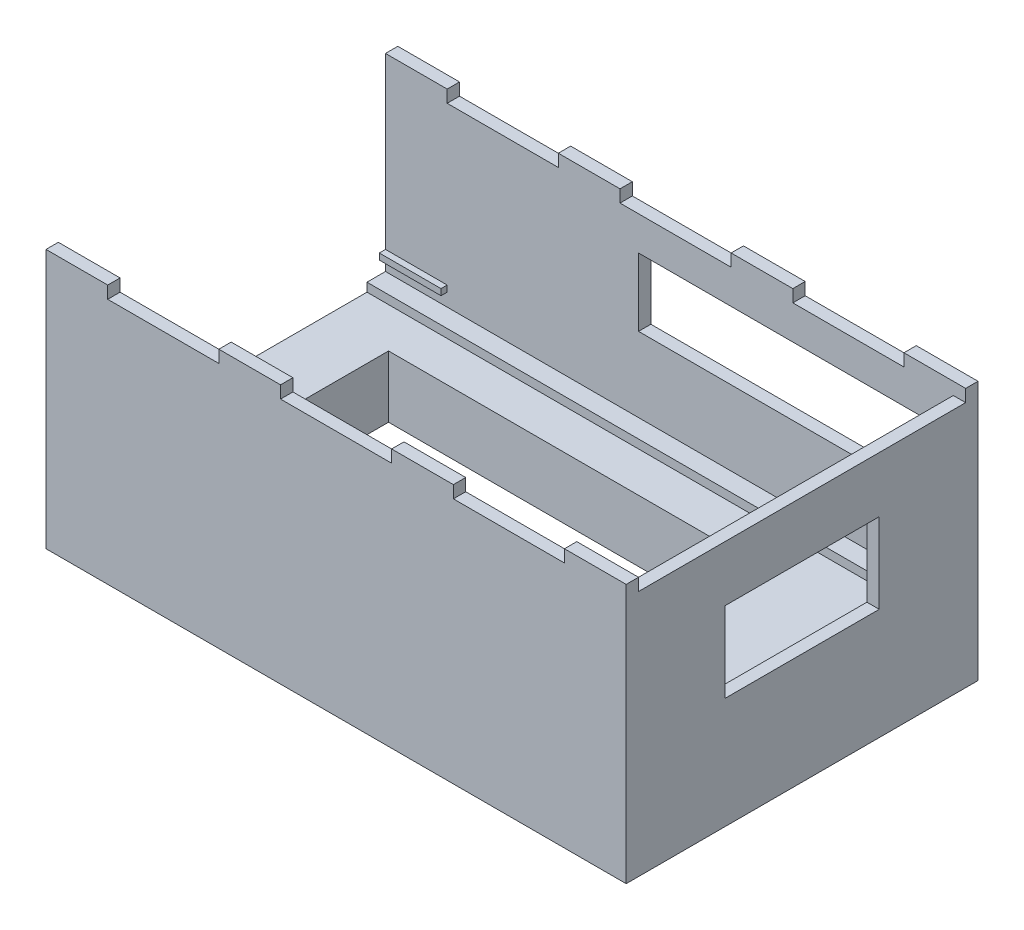
SolidWorks part; units mm, degrees
ref_plane "Front Plane" through (0, 0, 0) normal (0, 0, 1) x (1, 0, 0)
ref_plane "Top Plane" through (0, 0, 0) normal (0, 1, 0) x (1, 0, 0)
ref_plane "Right Plane" through (0, 0, 0) normal (1, 0, 0) x (0, 0, -1)
sketch "Sketch1" plane through (0, 0, 0) normal (0, 1, 0) x (1, 0, 0)
  line L1 (-30.298, 32.6459) -> (63.702, 32.6459)
  line L2 (-30.298, 32.6459) -> (-30.298, -24.3541)
  line L3 (-30.298, -24.3541) -> (63.702, -24.3541)
  line L4 (63.702, 32.6459) -> (63.702, -24.3541)
  dimension "D1" = 94
  dimension "D2" = 57
extrude "Boss-Extrude1" add sketch "Sketch1" along normal blind 10
sketch "Sketch2" plane through (0, 10, 0) normal (0, 1, 0) x (1, 0, 0)
  line L0 (-30.298, 32.6459) -> (63.702, 32.6459)
  line L1 (63.702, 32.6459) -> (63.702, -24.3541)
  line L2 (63.702, -24.3541) -> (-30.298, -24.3541)
  line L3 (-30.298, -24.3541) -> (-30.298, -22.3541)
  line L4 (-30.298, 32.6459) -> (-30.298, -24.3541) construction
  line L5 (-30.298, -22.3541) -> (61.702, -22.3541)
  line L6 (61.702, -22.3541) -> (61.702, 30.6459)
  line L7 (61.702, 30.6459) -> (-30.298, 30.6459)
  line L8 (-30.298, 30.6459) -> (-30.298, 32.6459)
  dimension "D1" = 2
  dimension "D2" = 2
  dimension "D3" = 2
extrude "Boss-Extrude2" add sketch "Sketch2" along normal blind 30
sketch "Sketch3" plane through (-30.298, 0, 0) normal (-1, 0, 0) x (0, 0, 1)
  line L0 (-30.6459, 40) -> (-30.6459, 10) construction
  line L1 (-30.6459, 10) -> (-27.6459, 10)
  line L2 (-30.6459, 10) -> (-30.6459, 11.4)
  line L3 (-30.6459, 11.4) -> (-27.6459, 11.4)
  line L4 (-27.6459, 10) -> (-27.6459, 11.4)
  line L5 (22.3541, 10) -> (19.3541, 10)
  line L6 (22.3541, 10) -> (22.3541, 11.4)
  line L7 (22.3541, 11.4) -> (19.3541, 11.4)
  line L8 (19.3541, 10) -> (19.3541, 11.4)
  line L9 (-30.6459, 14.5) -> (-29.6459, 14.5)
  line L10 (-30.6459, 14.5) -> (-30.6459, 13.5)
  line L11 (-30.6459, 13.5) -> (-29.6459, 13.5)
  line L12 (-29.6459, 14.5) -> (-29.6459, 13.5)
  line L13 (22.3541, 40) -> (22.3541, 10) construction
  line L14 (22.3541, 13.5) -> (21.3541, 13.5)
  line L15 (22.3541, 13.5) -> (22.3541, 14.5)
  line L16 (22.3541, 14.5) -> (21.3541, 14.5)
  line L17 (21.3541, 13.5) -> (21.3541, 14.5)
  point P22 (0, 0)
  dimension "D1" = 3
  dimension "D2" = 1.4
  dimension "D3" = 3
  dimension "D4" = 1.4
  dimension "D5" = 2.1
  dimension "D6" = 2.1
  dimension "D8" = 1
  dimension "D9" = 1
  dimension "D10" = 1
  dimension "D11" = 1
extrude "Boss-Extrude3" add sketch "Sketch3" against normal up to surface (92 mm away) contours L1 L4 L3 L2 | L5 L8 L7 L6 | L17 L16 L15 L14 up to face at (61.702, 25, -4.1459)
extrude "Boss-Extrude4" add sketch "Sketch3<3>" against normal blind 10 contours L12 L11 L10 L9
sketch "Sketch3<3>" plane through (-30.298, 0, 0) normal (-1, 0, 0) x (0, 0, 1) same geometry as "Sketch3"
sketch "Sketch4" plane through (0, 0, -32.6459) normal (0, 0, -1) x (-1, 0, 0)
  line L0 (-63.702, 40) -> (-63.702, 0) construction
  line L1 (-56.702, 34.5) -> (-10.702, 34.5)
  line L2 (-56.702, 34.5) -> (-56.702, 23.5)
  line L3 (-56.702, 23.5) -> (-10.702, 23.5)
  line L4 (-10.702, 34.5) -> (-10.702, 23.5)
  point P4 (-56.702, 29)
  dimension "D1" = 7
  dimension "D2" = 46
  dimension "D3" = 11
  dimension "D4" = 9
extrude "Cut-Extrude1" cut sketch "Sketch4" against normal blind 10
sketch "Sketch5" plane through (63.702, 0, 0) normal (1, 0, 0) x (0, 0, -1)
  line L0 (-24.3541, 40) -> (-24.3541, 0) construction
  line L1 (-8.3541, 31) -> (16.6459, 31)
  line L2 (-8.3541, 31) -> (-8.3541, 18)
  line L3 (-8.3541, 18) -> (16.6459, 18)
  line L4 (16.6459, 31) -> (16.6459, 18)
  line L5 (-24.3541, 40) -> (32.6459, 40) construction
  line L7 (32.6459, 40) -> (32.6459, 0) construction
  dimension "D1" = 16
  dimension "D2" = 16
  dimension "D3" = 9
  dimension "D4" = 13
extrude "Cut-Extrude2" cut sketch "Sketch5" against normal up to surface (2 mm away) up to face at (61.702, 16.8, 4.5207)
ref_plane "Plane5" through (0, 33, 0) normal (0, 1, 0) x (1, 0, 0)
sketch "Sketch7" plane through (0, 33, 0) normal (0, 1, 0) x (1, 0, 0)
  line L0 (61.702, -22.3541) -> (-30.298, -22.3541) construction
  line L1 (10.702, -22.3541) -> (61.702, -22.3541)
  line L2 (10.702, -22.3541) -> (10.702, -20.3541)
  line L3 (10.702, -20.3541) -> (59.702, -20.3541)
  line L4 (61.702, -22.3541) -> (61.702, -20.3541)
  line L5 (61.702, 27.6459) -> (61.702, -19.3541) construction
  line L6 (61.702, 30.6459) -> (61.702, -22.3541) construction
  line L8 (59.702, -20.3541) -> (59.702, 15.6459)
  line L9 (59.702, 15.6459) -> (61.702, 15.6459)
  line L10 (61.702, -20.3541) -> (61.702, 15.6459)
  dimension "D1" = 51
  dimension "D2" = 2
  dimension "D3" = 38
  dimension "D4" = 2
extrude "Boss-Extrude5" add sketch "Sketch7" against normal blind 2 contours L3 L8 L9 L10 L4 L1 L2
fillet "Fillet1" radius 1.5 2 edges at (59.702, 31, 2.3541) (35.202, 31, 20.3541) conic radius 3
ref_plane "Plane6" through (0, 34.8, 0) normal (0, 1, 0) x (1, 0, 0)
sketch "Sketch8" plane through (0, 34.8, 0) normal (0, 1, 0) x (1, 0, 0)
  line L1 (10.702, -20.3541) -> (59.702, -20.3541)
  line L2 (10.702, -20.3541) -> (10.702, -22.3541)
  line L3 (10.702, -22.3541) -> (61.702, -22.3541)
  line L4 (61.702, -20.3541) -> (61.702, -22.3541)
  line L5 (61.702, -22.3541) -> (59.702, -22.3541)
  line L6 (61.702, -22.3541) -> (61.702, 15.6459)
  line L7 (61.702, 15.6459) -> (59.702, 15.6459)
  line L8 (59.702, -20.3541) -> (59.702, 15.6459)
extrude "Boss-Extrude6" add sketch "Sketch8" along normal blind 1 contours L6 L7 L8 L1 L2 L3
sketch "Sketch9" plane through (0, 40, 0) normal (0, 1, 0) x (1, 0, 0)
  line L0 (-30.298, 30.6459) -> (61.702, 30.6459) construction
  line L1 (-30.298, 32.6459) -> (-20.298, 32.6459)
  line L2 (-30.298, 32.6459) -> (-30.298, 30.6459)
  line L3 (-30.298, 30.6459) -> (-20.298, 30.6459)
  line L4 (-20.298, 32.6459) -> (-20.298, 30.6459)
  line L5 (61.702, 30.6459) -> (-30.298, 30.6459) construction
  line L6 (-2.298, 30.6459) -> (7.702, 30.6459)
  line L7 (-2.298, 30.6459) -> (-2.298, 32.6459)
  line L8 (-2.298, 32.6459) -> (7.702, 32.6459)
  line L9 (7.702, 30.6459) -> (7.702, 32.6459)
  line L10 (63.702, 32.6459) -> (-30.298, 32.6459) construction
  line L11 (61.702, -22.3541) -> (-30.298, -22.3541) construction
  line L12 (25.702, 30.6459) -> (35.702, 30.6459)
  line L13 (25.702, 30.6459) -> (25.702, 32.6459)
  line L14 (25.702, 32.6459) -> (35.702, 32.6459)
  line L15 (35.702, 30.6459) -> (35.702, 32.6459)
  line L16 (53.702, 30.6459) -> (63.702, 30.6459)
  line L17 (53.702, 30.6459) -> (53.702, 32.6459)
  line L18 (53.702, 32.6459) -> (63.702, 32.6459)
  line L19 (63.702, 30.6459) -> (63.702, 32.6459)
  line L20 (-30.298, -24.3541) -> (-20.298, -24.3541)
  line L21 (-30.298, -24.3541) -> (-30.298, -22.3541)
  line L22 (-30.298, -22.3541) -> (-20.298, -22.3541)
  line L23 (-20.298, -24.3541) -> (-20.298, -22.3541)
  line L24 (-30.298, -24.3541) -> (63.702, -24.3541) construction
  line L25 (-2.298, -24.3541) -> (7.702, -24.3541)
  line L26 (-2.298, -24.3541) -> (-2.298, -22.3541)
  line L27 (-2.298, -22.3541) -> (7.702, -22.3541)
  line L28 (7.702, -24.3541) -> (7.702, -22.3541)
  line L29 (10.702, -22.3541) -> (61.702, -22.3541) construction
  line L30 (25.702, -24.3541) -> (35.702, -24.3541)
  line L31 (25.702, -24.3541) -> (25.702, -22.3541)
  line L32 (25.702, -22.3541) -> (35.702, -22.3541)
  line L33 (35.702, -24.3541) -> (35.702, -22.3541)
  line L35 (63.702, -24.3541) -> (53.702, -24.3541)
  line L36 (63.702, -24.3541) -> (63.702, -22.3541)
  line L37 (63.702, -22.3541) -> (53.702, -22.3541)
  line L38 (53.702, -24.3541) -> (53.702, -22.3541)
  dimension "D1" = 10
  dimension "D2" = 10
  dimension "D3" = 18
  dimension "D4" = 18
  dimension "D5" = 10
  dimension "D6" = 18
  dimension "D7" = 18
  dimension "D8" = 18
  dimension "D9" = 18
  dimension "D10" = 10
  dimension "D11" = 10
  dimension "D12" = 10
extrude "Boss-Extrude7" add sketch "Sketch9" along normal blind 2
sketch "Sketch10" plane through (0, 10, 0) normal (0, 1, 0) x (1, 0, 0)
  line L0 (-30.298, 4.1459) -> (61.702, 4.1459) construction
  line L1 (-20.298, 21.1459) -> (31.702, 21.1459)
  line L2 (-20.298, 21.1459) -> (-20.298, -12.8541)
  line L3 (-20.298, -12.8541) -> (31.702, -12.8541)
  line L4 (31.702, 21.1459) -> (31.702, -12.8541)
  line L5 (-30.298, 27.6459) -> (-30.298, -19.3541) construction
  line L6 (61.702, 30.6459) -> (61.702, -22.3541) construction
  point P10 (31.702, 4.1459)
  dimension "D1" = 34
  dimension "D2" = 0
  dimension "D3" = 52
  dimension "D4" = 10
extrude "Cut-Extrude3" cut sketch "Sketch10" against normal through all and the other way through all
